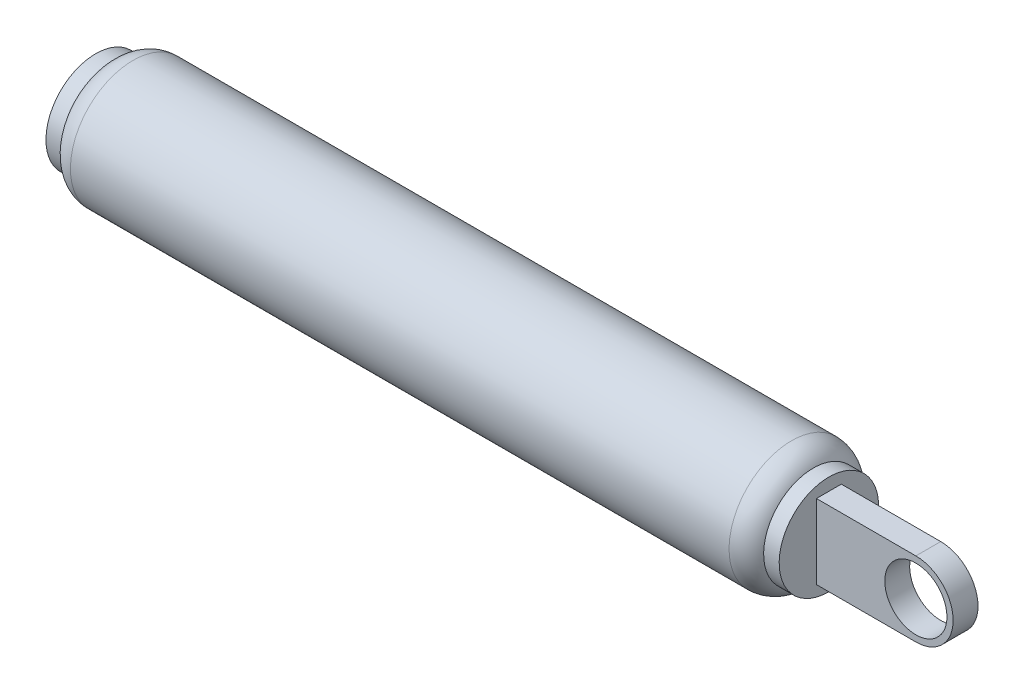
SolidWorks part; units mm, degrees
ref_plane "Front Plane" through (0, 0, 0) normal (0, 0, 1) x (1, 0, 0)
ref_plane "Top Plane" through (0, 0, 0) normal (0, 1, 0) x (1, 0, 0)
ref_plane "Right Plane" through (0, 0, 0) normal (1, 0, 0) x (0, 0, -1)
ref_plane "Plane1" through (0, 0, 0) normal (0, 0, -1) x (-1, 0, 0)
sketch "Sketch1" plane through (0, 0, 0) normal (0, 0, -1) x (-1, 0, 0)
  line L0 (-29.5, 4) -> (-29.5, 0)
  line L1 (-29.5, 0) -> (29.5, 0)
  line L2 (29.5, 0) -> (29.5, 4)
  line L3 (29.5, 4) -> (28.25, 4)
  line L4 (26.5, 5.0318) -> (-26.5, 5.0318)
  line L5 (-28.25, 4) -> (-29.5, 4)
  line L6 (-29.5, 0) -> (29.5, 0) construction
  arc A0 (28.25, 4) -> (26.5, 5.0318) centre (26.5, 3.0318) ccw
  arc A1 (-26.5, 5.0318) -> (-28.25, 4) centre (-26.5, 3.0318) ccw
  point P10 (0, 0)
  dimension "D5" = 2
  dimension "D1" = 4
  dimension "D2" = 53
  dimension "D3" = 1.25
  dimension "D4" = 59
revolve "Revolve1" add sketch "Sketch1" angle 360 about L6 reverse direction yes
ref_plane "Plane2" through (0, 0, 1) normal (0, 0, 1) x (1, 0, 0)
sketch "Sketch2" plane through (0, 0, 1) normal (0, 0, 1) x (1, 0, 0)
  line L0 (37.5, 3) -> (29.5, 3)
  line L1 (29.5, 3) -> (29.5, -3)
  line L2 (29.5, -3) -> (37.5, -3)
  line L5 (29.5, -4) -> (29.5, 4) construction
  arc A0 (37.5, -3) -> (37.5, 3) centre (37.5, 0) ccw
  point P8 (29.5, 0)
  dimension "D2" = 3
  dimension "D1" = 8
  dimension "D3" = 6
extrude "Boss-Extrude1" add sketch "Sketch2" against normal blind 2
hole_wizard "Ø6.0 (6) Diameter Hole1" positions "Sketch4" profile "Sketch3" hole size "Ø6.0" standard "ANSI Metric"
sketch "Sketch4" plane through (-29.5, 0, 0) normal (-1, 0, 0) x (0, 0, 1)
  point P0 (0, 0)
sketch "Sketch3" plane through (-29.5, 0, 0) normal (0, 1, 0) x (0, 0, 1)
  line L0 (0, 0) -> (0, 30)
  line L1 (0, 30) -> (3, 30)
  line L2 (3, 30) -> (3, 0)
  line L5 (3, 0) -> (0, 0)
  line L10 (0, 30) -> (-3, 30) construction
  line L11 (0, -6.35) -> (0, 107.95) construction
  dimension "Hole Dia." = 6
  dimension "Hole Depth" = 30
  dimension "Drill Angle" = 180
hole_wizard "Ø5.0 (5) Diameter Hole1" positions "Sketch6" profile "Sketch5" hole size "Ø5.0" standard "ANSI Metric"
sketch "Sketch6" plane through (0, 0, -1) normal (0, 0, -1) x (-1, 0, 0)
  arc A0 (-37.5, 3) -> (-37.5, -3) centre (-37.5, 0) ccw construction
  point P0 (-37.5, 0)
sketch "Sketch5" plane through (37.5, 0, -1) normal (1, 0, 0) x (0, 1, 0)
  line L0 (0, 0) -> (0, 6.0318)
  line L1 (0, 6.0318) -> (2.5, 6.0318)
  line L2 (2.5, 6.0318) -> (2.5, 0)
  line L5 (2.5, 0) -> (0, 0)
  line L11 (0, -6.35) -> (0, 107.95) construction
  dimension "Thru Hole Dia." = 5
  dimension "Thru Hole Depth" = 6.0318
ref_axis "Axis1" through (37.5, 0, 3.2933) along (0, 0, -1)
